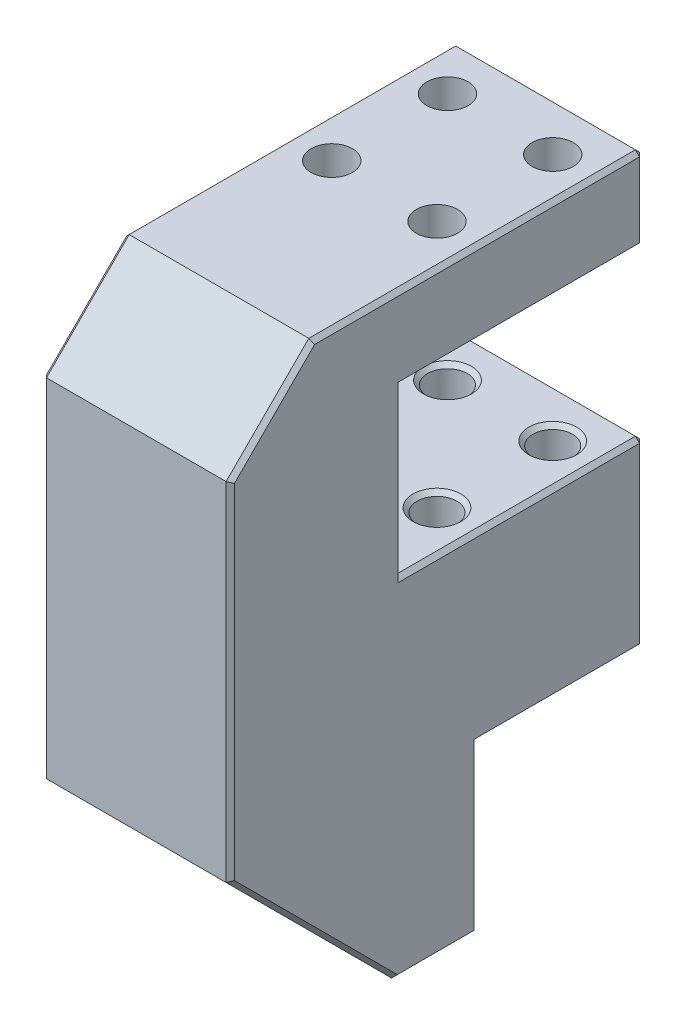
SolidWorks part; units mm, degrees
ref_plane "Front Plane" through (0, 0, 0) normal (0, 0, 1) x (1, 0, 0)
ref_plane "Top Plane" through (0, 0, 0) normal (0, 1, 0) x (1, 0, 0)
ref_plane "Right Plane" through (0, 0, 0) normal (1, 0, 0) x (0, 0, -1)
sketch "Sketch1" plane through (0, 0, 0) normal (0, 1, 0) x (1, 0, 0)
  line L1 (0, 0) -> (-12.73, 0)
  line L2 (0, 0) -> (0, 14)
  line L3 (0, 14) -> (-12.73, 14)
  line L4 (-12.73, 0) -> (-12.73, 14)
  line L5 (5, 20) -> (-17.73, 20)
  line L6 (5, 20) -> (5, -10)
  line L7 (5, -10) -> (-17.73, -10)
  line L8 (-17.73, 20) -> (-17.73, -10)
  circle A0 centre (-12.73, 14) radius 2.5
  circle A1 centre (0, 0) radius 2.5
  dimension "D3" = 5
  dimension "D1" = 14
  dimension "D2" = 12.73
  dimension "D4" = 5
  dimension "D5" = 5
  dimension "D6" = 20
  dimension "D7" = 10
sketch "Sketch2" plane through (0, 0, 0) normal (0, 1, 0) x (1, 0, 0)
  line L0 (5, 20) -> (-17.73, 20) construction
  line L1 (-17.73, 20) -> (-17.73, -10) construction
  line L2 (5, 20) -> (5, -10) construction
  line L3 (5, -10) -> (-17.73, -10) construction
  line L4 (5, 20) -> (-17.73, 20)
  line L5 (-17.73, 20) -> (-17.73, -10)
  line L6 (5, 20) -> (5, -10)
  line L7 (5, -10) -> (-17.73, -10)
extrude "Boss-Extrude1" add sketch "Sketch2" along normal blind 52
sketch "Sketch3" plane through (0, 0, 0) normal (0, -1, 0) x (1, 0, 0)
  line L0 (-17.73, -20) -> (-17.73, 10) construction
  line L1 (5, 10) -> (-17.73, 10)
  line L2 (5, 10) -> (5, 0)
  line L3 (5, 0) -> (-17.73, 0)
  line L4 (-17.73, 10) -> (-17.73, 0)
  dimension "D1" = 10
extrude "Boss-Extrude2" add sketch "Sketch3" along normal blind 20
sketch "Sketch4" plane through (0, 0, 10) normal (0, 0, 1) x (1, 0, 0)
  line L0 (-6.365, 0) -> (-6.365, -20) construction
  line L1 (5, -20) -> (-17.73, -20) construction
  line L2 (0, 0) -> (-6.365, 0) construction
  point P4 (-6.365, -10)
  point P6 (-6.365, -10)
  dimension "D1" = 10
  dimension "D2" = 10
hole_wizard "CBORE for M5 SHCS1" positions "Sketch5" profile "Sketch6" counterbore size "M5" standard "ANSI Metric" end condition through all
sketch "Sketch5" plane through (0, 0, 10) normal (0, 0, 1) x (1, 0, 0)
  point P3 (-6.365, -10)
  point P7 (0, 0)
sketch "Sketch6" plane through (-6.365, -10, 10) normal (1, 0, 0) x (0, -1, 0)
  line L0 (0, 0) -> (0, 30)
  line L1 (0, 30) -> (2.75, 30)
  line L3 (2.75, 30) -> (2.75, 5)
  line L4 (2.75, 5) -> (5, 5)
  line L5 (5, 5) -> (5, 0)
  line L7 (5, 0) -> (0, 0)
  line L11 (0, -6.35) -> (0, 107.95) construction
  dimension "Thru Hole Dia." = 5.5
  dimension "Thru Hole Depth" = 30
  dimension "C'Bore Dia." = 10
  dimension "C'Bore Depth" = 5
sketch "Sketch7" plane through (0, 0, 10) normal (0, 0, 1) x (1, 0, 0)
  line L4 (-17.73, 52) -> (-17.73, -20)
  line L5 (-17.73, -20) -> (5, -20)
  line L6 (5, -20) -> (5, 52)
  line L7 (5, 52) -> (-17.73, 52)
  line L8 (-17.73, 52) -> (-17.73, -20)
  line L9 (-17.73, -20) -> (5, -20)
  line L10 (5, -20) -> (5, 52)
  line L11 (5, 52) -> (-17.73, 52)
  circle A4 centre (-6.365, -10) radius 5 construction
  circle A5 centre (-6.365, -10) radius 5
  dimension "D1" = 0
extrude "Boss-Extrude3" add sketch "Sketch7" along normal blind 20
sketch "Sketch8" plane through (5, 0, 0) normal (1, 0, 0) x (0, 0, -1)
  line L0 (20, 52) -> (20, 0) construction
  line L1 (20, 42) -> (-9.2, 42)
  line L2 (20, 42) -> (20, 22)
  line L3 (20, 22) -> (-9.2, 22)
  line L4 (-9.2, 42) -> (-9.2, 22)
  line L5 (-30, 52) -> (20, 52) construction
  dimension "D1" = 20
  dimension "D2" = 10
  dimension "D3" = 9.2
extrude "Cut-Extrude1" cut sketch "Sketch8" against normal through all
sketch "Sketch9" plane through (0, 52, 0) normal (0, 1, 0) x (1, 0, 0)
  circle A1 centre (-12.73, 0) radius 2.5
  circle A2 centre (0, 14) radius 2.5
  circle A3 centre (-12.73, 14) radius 2.5
  circle A4 centre (0, 0) radius 2.5
  dimension "D1" = 5
extrude "Cut-Extrude2" cut sketch "Sketch9" against normal up to next
sketch "Sketch10" plane through (0, 22, 0) normal (0, 1, 0) x (1, 0, 0)
  circle A0 centre (0, 0) radius 2.4
  circle A1 centre (-12.73, 0) radius 2.4
  circle A2 centre (-12.73, 14) radius 2.4
  circle A3 centre (0, 14) radius 2.4
  dimension "D1" = 4.8
extrude "Cut-Extrude3" cut sketch "Sketch10" against normal blind 20
sketch "Sketch11" plane through (5, 0, 0) normal (1, 0, 0) x (0, 0, -1)
  line L10 (20, 0) -> (20, 22)
  line L11 (20, 22) -> (-9.2, 22)
  line L12 (-9.2, 22) -> (-9.2, 42)
  line L13 (-9.2, 42) -> (20, 42)
  line L14 (20, 42) -> (20, 52)
  line L15 (20, 52) -> (-30, 52)
  line L16 (-30, 52) -> (-30, -20)
  line L17 (-30, -20) -> (0, -20)
  line L18 (0, -20) -> (0, 0)
  line L19 (0, 0) -> (20, 0)
  line L20 (20, 0) -> (20, 22)
  line L21 (20, 22) -> (-9.2, 22)
  line L22 (-9.2, 22) -> (-9.2, 42)
  line L23 (-9.2, 42) -> (20, 42)
  line L24 (20, 42) -> (20, 52)
  line L25 (20, 52) -> (-30, 52)
  line L26 (-30, 52) -> (-30, -20)
  line L27 (-30, -20) -> (0, -20)
  line L28 (0, -20) -> (0, 0)
  line L29 (0, 0) -> (20, 0)
  dimension "D1" = 0
sketch "Sketch12" plane through (0, 0, -20) normal (0, 0, -1) x (-1, 0, 0)
  line L0 (-5, 0) -> (17.73, 0) construction
  line L1 (17.73, 22) -> (37.73, 22)
  line L2 (17.73, 22) -> (17.73, 0)
  line L3 (17.73, 0) -> (37.73, 0)
  line L4 (37.73, 22) -> (37.73, 0)
  dimension "D1" = 20
extrude "Boss-Extrude5" add sketch "Sketch12" against normal blind 20
sketch "Sketch13" plane through (0, 22, 0) normal (0, 1, 0) x (1, 0, 0)
  line L0 (-17.73, 0) -> (-37.73, 20) construction
hole_wizard "CBORE for M5 SHCS2" positions "Sketch14" profile "Sketch15" counterbore size "M5" standard "ANSI Metric" end condition through all
sketch "Sketch14" plane through (0, 22, 0) normal (0, 1, 0) x (1, 0, 0)
  line L0 (-17.73, 0) -> (-37.73, 20) construction
  point P0 (-27.73, 10)
  point P5 (0, 0)
sketch "Sketch15" plane through (-27.73, 22, -10) normal (1, 0, 0) x (0, 0, 1)
  line L0 (0, 0) -> (0, 42)
  line L1 (0, 42) -> (2.75, 42)
  line L3 (2.75, 42) -> (2.75, 16)
  line L4 (2.75, 16) -> (5, 16)
  line L5 (5, 16) -> (5, 0)
  line L7 (5, 0) -> (0, 0)
  line L11 (0, -6.35) -> (0, 107.95) construction
  dimension "Thru Hole Dia." = 5.5
  dimension "Thru Hole Depth" = 42
  dimension "C'Bore Dia." = 10
  dimension "C'Bore Depth" = 16
chamfer "Chamfer1" distance 20 angle 45 2 edges at (-6.365, -20, 30) (-37.73, 22, -10)
chamfer "Chamfer3" distance 10 angle 45 1 edges at (-6.365, 52, 30)
chamfer "Chamfer2" distance 0.5 angle 45 31 edges at (5, 52, 0) (5, 11, -20) (5, 47, -20) (5, 0, -10) (5, -10, 0) (5, -20, 5) (5, -10, 20) (5, 21, 30) (-17.73, -10, 0) (-17.73, 52, 0) (-17.73, 21, 30) (-17.73, -10, 20) (-17.73, -20, 5) (5, 42, -5.4) (5, 32, 9.2) (5, 22, -5.4) (-17.73, 47, -20) (-17.73, 22, 4.6) (-17.73, 32, 9.2) (-17.73, 42, -5.4) (0, 22, -11.6) (-12.73, 22, -11.6) (-12.73, 22, 2.4) (0, 22, 2.4) (5, 47, 25) (-17.73, 47, 25) (-37.73, 1, -20) (-27.73, 12, -20) (-6.365, 22, -20) (-6.365, 42, -20) (-6.365, 52, -20)
